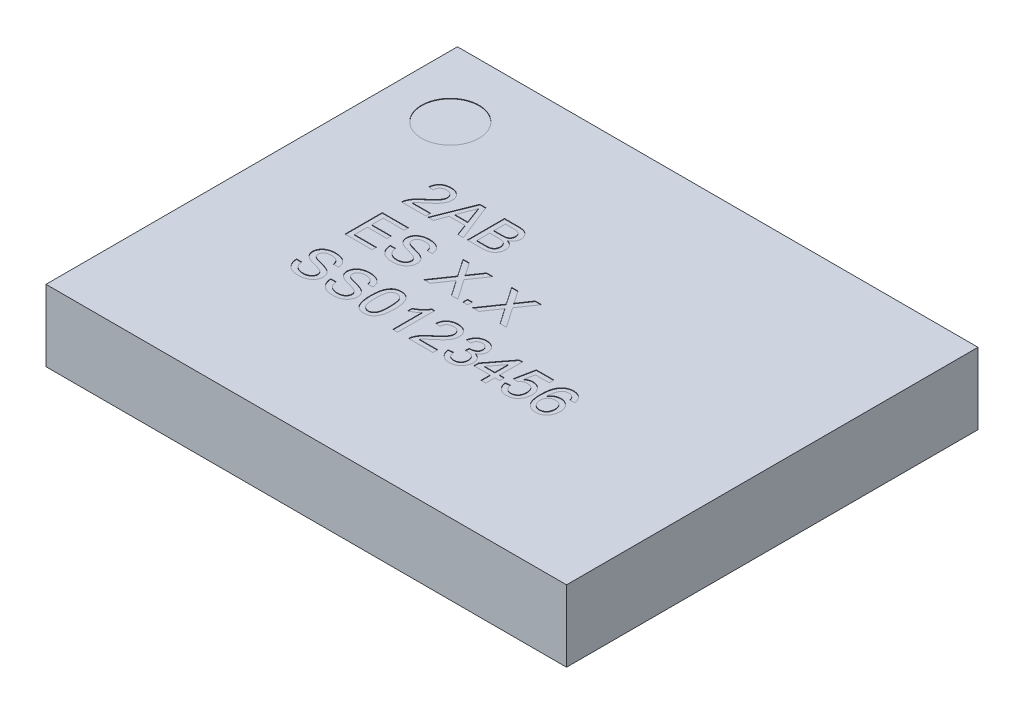
SolidWorks part; units mm, degrees
ref_plane "Front Plane" through (0, 0, 0) normal (0, 0, 1) x (1, 0, 0)
ref_plane "Top Plane" through (0, 0, 0) normal (0, 1, 0) x (1, 0, 0)
ref_plane "Right Plane" through (0, 0, 0) normal (1, 0, 0) x (0, 0, -1)
sketch "Sketch1" plane through (0, 0, 0) normal (0, 1, 0) x (1, 0, 0)
  line L1 (-5.25, -4.15) -> (5.25, -4.15)
  line L2 (-5.25, -4.15) -> (-5.25, 4.15)
  line L3 (-5.25, 4.15) -> (5.25, 4.15)
  line L4 (5.25, -4.15) -> (5.25, 4.15)
  line L5 (-5.25, -4.15) -> (5.25, 4.15) construction
  line L6 (-5.25, 4.15) -> (5.25, -4.15) construction
  point P0 (0, 0)
  dimension "D1" = 10.5
  dimension "D2" = 8.3
extrude "Boss-Extrude1" add sketch "Sketch1" along normal blind 1.44
sketch "Sketch3" plane through (0, 0, 0) normal (0, -1, 0) x (1, 0, 0)
  line L0 (-5.25, 4.15) -> (5.25, 4.15) construction
  line L1 (-4.95, 2.85) -> (-4.5, 2.85)
  line L2 (-4.95, 2.85) -> (-4.95, 3.15)
  line L3 (-4.95, 3.15) -> (-4.5, 3.15)
  line L4 (-4.5, 2.85) -> (-4.5, 3.15)
  line L5 (-4.95, 2.85) -> (-4.5, 3.15) construction
  line L6 (-4.95, 3.15) -> (-4.5, 2.85) construction
  line L7 (-5.25, -4.15) -> (-5.25, 4.15) construction
  line L8 (-4.95, 2.25) -> (-4.95, 2.55)
  line L9 (-4.95, 2.25) -> (-4.5, 2.25)
  line L10 (-4.5, 2.25) -> (-4.5, 2.55)
  line L11 (-4.95, 2.55) -> (-4.5, 2.55)
  line L12 (-4.95, 1.65) -> (-4.95, 1.95)
  line L13 (-4.95, 1.65) -> (-4.5, 1.65)
  line L14 (-4.5, 1.65) -> (-4.5, 1.95)
  line L15 (-4.95, 1.95) -> (-4.5, 1.95)
  line L16 (-4.95, 1.05) -> (-4.95, 1.35)
  line L17 (-4.95, 1.05) -> (-4.5, 1.05)
  line L18 (-4.5, 1.05) -> (-4.5, 1.35)
  line L19 (-4.95, 1.35) -> (-4.5, 1.35)
  line L20 (-4.95, 0.45) -> (-4.95, 0.75)
  line L21 (-4.95, 0.45) -> (-4.5, 0.45)
  line L22 (-4.5, 0.45) -> (-4.5, 0.75)
  line L23 (-4.95, 0.75) -> (-4.5, 0.75)
  line L24 (-4.95, -0.15) -> (-4.95, 0.15)
  line L25 (-4.95, -0.15) -> (-4.5, -0.15)
  line L26 (-4.5, -0.15) -> (-4.5, 0.15)
  line L27 (-4.95, 0.15) -> (-4.5, 0.15)
  line L28 (-4.95, -0.75) -> (-4.95, -0.45)
  line L29 (-4.95, -0.75) -> (-4.5, -0.75)
  line L30 (-4.5, -0.75) -> (-4.5, -0.45)
  line L31 (-4.95, -0.45) -> (-4.5, -0.45)
  line L32 (-4.95, -1.35) -> (-4.95, -1.05)
  line L33 (-4.95, -1.35) -> (-4.5, -1.35)
  line L34 (-4.5, -1.35) -> (-4.5, -1.05)
  line L35 (-4.95, -1.05) -> (-4.5, -1.05)
  line L36 (-4.95, -1.95) -> (-4.95, -1.65)
  line L37 (-4.95, -1.95) -> (-4.5, -1.95)
  line L38 (-4.5, -1.95) -> (-4.5, -1.65)
  line L39 (-4.95, -1.65) -> (-4.5, -1.65)
  line L40 (-4.95, -2.55) -> (-4.95, -2.25)
  line L41 (-4.95, -2.55) -> (-4.5, -2.55)
  line L42 (-4.5, -2.55) -> (-4.5, -2.25)
  line L43 (-4.95, -2.25) -> (-4.5, -2.25)
  line L44 (-4.95, -3.15) -> (-4.95, -2.85)
  line L45 (-4.95, -3.15) -> (-4.5, -3.15)
  line L46 (-4.5, -3.15) -> (-4.5, -2.85)
  line L47 (-4.95, -2.85) -> (-4.5, -2.85)
  line L48 (-4.35, 3.4) -> (-5.25, 3.4) construction
  line L49 (4.5, 2.85) -> (4.95, 2.85)
  line L50 (4.5, 2.85) -> (4.5, 3.15)
  line L51 (4.5, 3.15) -> (4.95, 3.15)
  line L52 (4.95, 2.85) -> (4.95, 3.15)
  line L53 (4.5, 2.85) -> (4.95, 3.15) construction
  line L54 (4.5, 3.15) -> (4.95, 2.85) construction
  line L55 (-4.35, 3.4) -> (-4.05, 3.4)
  line L56 (4.95, 3.15) -> (5.25, 3.15) construction
  line L57 (5.25, 4.15) -> (5.25, -4.15) construction
  line L58 (-4.95, 3.15) -> (-5.25, 3.15) construction
  line L59 (4.95, 3.15) -> (4.95, 4.15) construction
  line L60 (-4.5, 3.15) -> (-4.5, 4.15) construction
  line L61 (-4.95, 2.55) -> (-4.95, 2.85) construction
  line L62 (4.5, 2.25) -> (4.95, 2.25)
  line L63 (4.95, 2.25) -> (4.95, 2.55)
  line L64 (4.5, 2.55) -> (4.95, 2.55)
  line L65 (4.5, 2.25) -> (4.5, 2.55)
  line L66 (4.5, 1.65) -> (4.95, 1.65)
  line L67 (4.95, 1.65) -> (4.95, 1.95)
  line L68 (4.5, 1.95) -> (4.95, 1.95)
  line L69 (4.5, 1.65) -> (4.5, 1.95)
  line L70 (4.5, 1.05) -> (4.95, 1.05)
  line L71 (4.95, 1.05) -> (4.95, 1.35)
  line L72 (4.5, 1.35) -> (4.95, 1.35)
  line L73 (4.5, 1.05) -> (4.5, 1.35)
  line L74 (4.5, 0.45) -> (4.95, 0.45)
  line L75 (4.95, 0.45) -> (4.95, 0.75)
  line L76 (4.5, 0.75) -> (4.95, 0.75)
  line L77 (4.5, 0.45) -> (4.5, 0.75)
  line L78 (4.5, -0.15) -> (4.95, -0.15)
  line L79 (4.95, -0.15) -> (4.95, 0.15)
  line L80 (4.5, 0.15) -> (4.95, 0.15)
  line L81 (4.5, -0.15) -> (4.5, 0.15)
  line L82 (4.5, -0.75) -> (4.95, -0.75)
  line L83 (4.95, -0.75) -> (4.95, -0.45)
  line L84 (4.5, -0.45) -> (4.95, -0.45)
  line L85 (4.5, -0.75) -> (4.5, -0.45)
  line L86 (4.5, -1.35) -> (4.95, -1.35)
  line L87 (4.95, -1.35) -> (4.95, -1.05)
  line L88 (4.5, -1.05) -> (4.95, -1.05)
  line L89 (4.5, -1.35) -> (4.5, -1.05)
  line L90 (4.5, -1.95) -> (4.95, -1.95)
  line L91 (4.95, -1.95) -> (4.95, -1.65)
  line L92 (4.5, -1.65) -> (4.95, -1.65)
  line L93 (4.5, -1.95) -> (4.5, -1.65)
  line L94 (4.5, -2.55) -> (4.95, -2.55)
  line L95 (4.95, -2.55) -> (4.95, -2.25)
  line L96 (4.5, -2.25) -> (4.95, -2.25)
  line L97 (4.5, -2.55) -> (4.5, -2.25)
  line L98 (4.5, -3.15) -> (4.95, -3.15)
  line L99 (4.95, -3.15) -> (4.95, -2.85)
  line L100 (4.5, -2.85) -> (4.95, -2.85)
  line L101 (4.5, -3.15) -> (4.5, -2.85)
  line L102 (4.5, 2.55) -> (4.5, 2.85) construction
  line L103 (-4.35, -3.85) -> (-5.25, -3.85) construction
  line L104 (-4.35, -3.85) -> (-4.05, -3.85)
  line L105 (-4.35, -3.85) -> (-4.35, -3.4)
  line L106 (-4.35, -3.4) -> (-4.05, -3.4)
  line L107 (-4.05, -3.85) -> (-4.05, -3.4)
  line L108 (-4.35, -3.85) -> (-4.05, -3.4) construction
  line L109 (-4.35, -3.4) -> (-4.05, -3.85) construction
  line L110 (-4.35, -3.85) -> (-4.35, -4.15) construction
  line L111 (5.25, -4.15) -> (-5.25, -4.15) construction
  line L112 (-4.35, 3.4) -> (-4.35, 3.85)
  line L113 (-4.35, 3.85) -> (-4.05, 3.85)
  line L114 (-4.05, 3.4) -> (-4.05, 3.85)
  line L115 (-4.35, 3.4) -> (-4.05, 3.85) construction
  line L116 (-4.35, 3.85) -> (-4.05, 3.4) construction
  line L117 (-4.05, 3.85) -> (-4.05, 4.15) construction
  line L118 (-3.75, 3.4) -> (-3.45, 3.4)
  line L119 (-3.45, 3.4) -> (-3.45, 3.85)
  line L120 (-3.75, 3.85) -> (-3.45, 3.85)
  line L121 (-3.75, 3.4) -> (-3.75, 3.85)
  line L122 (-3.75, -3.85) -> (-3.75, -3.4)
  line L123 (-3.75, -3.85) -> (-3.45, -3.85)
  line L124 (-3.45, -3.85) -> (-3.45, -3.4)
  line L125 (-3.75, -3.4) -> (-3.45, -3.4)
  line L126 (-3.15, 3.4) -> (-2.85, 3.4)
  line L127 (-2.85, 3.4) -> (-2.85, 3.85)
  line L128 (-3.15, 3.85) -> (-2.85, 3.85)
  line L129 (-3.15, 3.4) -> (-3.15, 3.85)
  line L130 (-3.15, -3.85) -> (-3.15, -3.4)
  line L131 (-3.15, -3.85) -> (-2.85, -3.85)
  line L132 (-2.85, -3.85) -> (-2.85, -3.4)
  line L133 (-3.15, -3.4) -> (-2.85, -3.4)
  line L134 (-2.55, 3.4) -> (-2.25, 3.4)
  line L135 (-2.25, 3.4) -> (-2.25, 3.85)
  line L136 (-2.55, 3.85) -> (-2.25, 3.85)
  line L137 (-2.55, 3.4) -> (-2.55, 3.85)
  line L138 (-2.55, -3.85) -> (-2.55, -3.4)
  line L139 (-2.55, -3.85) -> (-2.25, -3.85)
  line L140 (-2.25, -3.85) -> (-2.25, -3.4)
  line L141 (-2.55, -3.4) -> (-2.25, -3.4)
  line L142 (-1.95, 3.4) -> (-1.65, 3.4)
  line L143 (-1.65, 3.4) -> (-1.65, 3.85)
  line L144 (-1.95, 3.85) -> (-1.65, 3.85)
  line L145 (-1.95, 3.4) -> (-1.95, 3.85)
  line L146 (-1.95, -3.85) -> (-1.95, -3.4)
  line L147 (-1.95, -3.85) -> (-1.65, -3.85)
  line L148 (-1.65, -3.85) -> (-1.65, -3.4)
  line L149 (-1.95, -3.4) -> (-1.65, -3.4)
  line L150 (-1.35, 3.4) -> (-1.05, 3.4)
  line L151 (-1.05, 3.4) -> (-1.05, 3.85)
  line L152 (-1.35, 3.85) -> (-1.05, 3.85)
  line L153 (-1.35, 3.4) -> (-1.35, 3.85)
  line L154 (-1.35, -3.85) -> (-1.35, -3.4)
  line L155 (-1.35, -3.85) -> (-1.05, -3.85)
  line L156 (-1.05, -3.85) -> (-1.05, -3.4)
  line L157 (-1.35, -3.4) -> (-1.05, -3.4)
  line L158 (-0.75, 3.4) -> (-0.45, 3.4)
  line L159 (-0.45, 3.4) -> (-0.45, 3.85)
  line L160 (-0.75, 3.85) -> (-0.45, 3.85)
  line L161 (-0.75, 3.4) -> (-0.75, 3.85)
  line L162 (-0.75, -3.85) -> (-0.75, -3.4)
  line L163 (-0.75, -3.85) -> (-0.45, -3.85)
  line L164 (-0.45, -3.85) -> (-0.45, -3.4)
  line L165 (-0.75, -3.4) -> (-0.45, -3.4)
  line L166 (-0.15, 3.4) -> (0.15, 3.4)
  line L167 (0.15, 3.4) -> (0.15, 3.85)
  line L168 (-0.15, 3.85) -> (0.15, 3.85)
  line L169 (-0.15, 3.4) -> (-0.15, 3.85)
  line L170 (-0.15, -3.85) -> (-0.15, -3.4)
  line L171 (-0.15, -3.85) -> (0.15, -3.85)
  line L172 (0.15, -3.85) -> (0.15, -3.4)
  line L173 (-0.15, -3.4) -> (0.15, -3.4)
  line L174 (0.45, 3.4) -> (0.75, 3.4)
  line L175 (0.75, 3.4) -> (0.75, 3.85)
  line L176 (0.45, 3.85) -> (0.75, 3.85)
  line L177 (0.45, 3.4) -> (0.45, 3.85)
  line L178 (0.45, -3.85) -> (0.45, -3.4)
  line L179 (0.45, -3.85) -> (0.75, -3.85)
  line L180 (0.75, -3.85) -> (0.75, -3.4)
  line L181 (0.45, -3.4) -> (0.75, -3.4)
  line L182 (1.05, 3.4) -> (1.35, 3.4)
  line L183 (1.35, 3.4) -> (1.35, 3.85)
  line L184 (1.05, 3.85) -> (1.35, 3.85)
  line L185 (1.05, 3.4) -> (1.05, 3.85)
  line L186 (1.05, -3.85) -> (1.05, -3.4)
  line L187 (1.05, -3.85) -> (1.35, -3.85)
  line L188 (1.35, -3.85) -> (1.35, -3.4)
  line L189 (1.05, -3.4) -> (1.35, -3.4)
  line L190 (1.65, 3.4) -> (1.95, 3.4)
  line L191 (1.95, 3.4) -> (1.95, 3.85)
  line L192 (1.65, 3.85) -> (1.95, 3.85)
  line L193 (1.65, 3.4) -> (1.65, 3.85)
  line L194 (1.65, -3.85) -> (1.65, -3.4)
  line L195 (1.65, -3.85) -> (1.95, -3.85)
  line L196 (1.95, -3.85) -> (1.95, -3.4)
  line L197 (1.65, -3.4) -> (1.95, -3.4)
  line L198 (2.25, 3.4) -> (2.55, 3.4)
  line L199 (2.55, 3.4) -> (2.55, 3.85)
  line L200 (2.25, 3.85) -> (2.55, 3.85)
  line L201 (2.25, 3.4) -> (2.25, 3.85)
  line L202 (2.25, -3.85) -> (2.25, -3.4)
  line L203 (2.25, -3.85) -> (2.55, -3.85)
  line L204 (2.55, -3.85) -> (2.55, -3.4)
  line L205 (2.25, -3.4) -> (2.55, -3.4)
  line L206 (2.85, 3.4) -> (3.15, 3.4)
  line L207 (3.15, 3.4) -> (3.15, 3.85)
  line L208 (2.85, 3.85) -> (3.15, 3.85)
  line L209 (2.85, 3.4) -> (2.85, 3.85)
  line L210 (2.85, -3.85) -> (2.85, -3.4)
  line L211 (2.85, -3.85) -> (3.15, -3.85)
  line L212 (3.15, -3.85) -> (3.15, -3.4)
  line L213 (2.85, -3.4) -> (3.15, -3.4)
  line L214 (3.45, 3.4) -> (3.75, 3.4)
  line L215 (3.75, 3.4) -> (3.75, 3.85)
  line L216 (3.45, 3.85) -> (3.75, 3.85)
  line L217 (3.45, 3.4) -> (3.45, 3.85)
  line L218 (3.45, -3.85) -> (3.45, -3.4)
  line L219 (3.45, -3.85) -> (3.75, -3.85)
  line L220 (3.75, -3.85) -> (3.75, -3.4)
  line L221 (3.45, -3.4) -> (3.75, -3.4)
  line L222 (4.05, 3.4) -> (4.35, 3.4)
  line L223 (4.35, 3.4) -> (4.35, 3.85)
  line L224 (4.05, 3.85) -> (4.35, 3.85)
  line L225 (4.05, 3.4) -> (4.05, 3.85)
  line L226 (4.05, -3.85) -> (4.05, -3.4)
  line L227 (4.05, -3.85) -> (4.35, -3.85)
  line L228 (4.35, -3.85) -> (4.35, -3.4)
  line L229 (4.05, -3.4) -> (4.35, -3.4)
  line L230 (-3.75, -2.85) -> (-3.3, -2.85)
  line L231 (-3.75, -2.85) -> (-3.75, -2.55)
  line L232 (-3.75, -2.55) -> (-3.3, -2.55)
  line L233 (-3.3, -2.85) -> (-3.3, -2.55)
  line L234 (-3.75, -2.85) -> (-3.3, -2.55) construction
  line L235 (-3.75, -2.55) -> (-3.3, -2.85) construction
  line L236 (-4.5, -2.55) -> (-4.5, -2.85) construction
  line L237 (3.3, -2.85) -> (3.75, -2.85)
  line L238 (3.3, -2.85) -> (3.3, -2.55)
  line L239 (3.3, -2.55) -> (3.75, -2.55)
  line L240 (3.75, -2.85) -> (3.75, -2.55)
  line L241 (3.3, -2.85) -> (3.75, -2.55) construction
  line L242 (3.3, -2.55) -> (3.75, -2.85) construction
  line L243 (3.75, -2.85) -> (5.25, -2.85) construction
  line L244 (-3.75, -2.85) -> (-5.25, -2.85) construction
  line L245 (-3.75, -2.25) -> (-3.3, -2.25)
  line L246 (-3.3, -2.25) -> (-3.3, -1.95)
  line L247 (-3.75, -1.95) -> (-3.3, -1.95)
  line L248 (-3.75, -2.25) -> (-3.75, -1.95)
  line L249 (3.3, -2.25) -> (3.75, -2.25)
  line L250 (3.75, -2.25) -> (3.75, -1.95)
  line L251 (3.3, -1.95) -> (3.75, -1.95)
  line L252 (3.3, -2.25) -> (3.3, -1.95)
  line L253 (-3.75, -1.65) -> (-3.3, -1.65)
  line L254 (-3.3, -1.65) -> (-3.3, -1.35)
  line L255 (-3.75, -1.35) -> (-3.3, -1.35)
  line L256 (-3.75, -1.65) -> (-3.75, -1.35)
  line L257 (3.3, -1.65) -> (3.75, -1.65)
  line L258 (3.75, -1.65) -> (3.75, -1.35)
  line L259 (3.3, -1.35) -> (3.75, -1.35)
  line L260 (3.3, -1.65) -> (3.3, -1.35)
  line L261 (-3.75, -1.05) -> (-3.3, -1.05)
  line L262 (-3.3, -1.05) -> (-3.3, -0.75)
  line L263 (-3.75, -0.75) -> (-3.3, -0.75)
  line L264 (-3.75, -1.05) -> (-3.75, -0.75)
  line L265 (3.3, -1.05) -> (3.75, -1.05)
  line L266 (3.75, -1.05) -> (3.75, -0.75)
  line L267 (3.3, -0.75) -> (3.75, -0.75)
  line L268 (3.3, -1.05) -> (3.3, -0.75)
  line L269 (-3.75, -0.45) -> (-3.3, -0.45)
  line L270 (-3.3, -0.45) -> (-3.3, -0.15)
  line L271 (-3.75, -0.15) -> (-3.3, -0.15)
  line L272 (-3.75, -0.45) -> (-3.75, -0.15)
  line L273 (3.3, -0.45) -> (3.75, -0.45)
  line L274 (3.75, -0.45) -> (3.75, -0.15)
  line L275 (3.3, -0.15) -> (3.75, -0.15)
  line L276 (3.3, -0.45) -> (3.3, -0.15)
  line L277 (-3.75, 0.15) -> (-3.3, 0.15)
  line L278 (-3.3, 0.15) -> (-3.3, 0.45)
  line L279 (-3.75, 0.45) -> (-3.3, 0.45)
  line L280 (-3.75, 0.15) -> (-3.75, 0.45)
  line L281 (3.3, 0.15) -> (3.75, 0.15)
  line L282 (3.75, 0.15) -> (3.75, 0.45)
  line L283 (3.3, 0.45) -> (3.75, 0.45)
  line L284 (3.3, 0.15) -> (3.3, 0.45)
  line L285 (-3.75, 0.75) -> (-3.3, 0.75)
  line L286 (-3.3, 0.75) -> (-3.3, 1.05)
  line L287 (-3.75, 1.05) -> (-3.3, 1.05)
  line L288 (-3.75, 0.75) -> (-3.75, 1.05)
  line L289 (3.3, 0.75) -> (3.75, 0.75)
  line L290 (3.75, 0.75) -> (3.75, 1.05)
  line L291 (3.3, 1.05) -> (3.75, 1.05)
  line L292 (3.3, 0.75) -> (3.3, 1.05)
  line L293 (-3.75, 1.35) -> (-3.3, 1.35)
  line L294 (-3.3, 1.35) -> (-3.3, 1.65)
  line L295 (-3.75, 1.65) -> (-3.3, 1.65)
  line L296 (-3.75, 1.35) -> (-3.75, 1.65)
  line L297 (3.3, 1.35) -> (3.75, 1.35)
  line L298 (3.75, 1.35) -> (3.75, 1.65)
  line L299 (3.3, 1.65) -> (3.75, 1.65)
  line L300 (3.3, 1.35) -> (3.3, 1.65)
  line L301 (-3.75, 1.95) -> (-3.3, 1.95)
  line L302 (-3.3, 1.95) -> (-3.3, 2.25)
  line L303 (-3.75, 2.25) -> (-3.3, 2.25)
  line L304 (-3.75, 1.95) -> (-3.75, 2.25)
  line L305 (3.3, 1.95) -> (3.75, 1.95)
  line L306 (3.75, 1.95) -> (3.75, 2.25)
  line L307 (3.3, 2.25) -> (3.75, 2.25)
  line L308 (3.3, 1.95) -> (3.3, 2.25)
  line L309 (-3.75, 2.55) -> (-3.3, 2.55)
  line L310 (-3.3, 2.55) -> (-3.3, 2.85)
  line L311 (-3.75, 2.85) -> (-3.3, 2.85)
  line L312 (-3.75, 2.55) -> (-3.75, 2.85)
  line L313 (3.3, 2.55) -> (3.75, 2.55)
  line L314 (3.75, 2.55) -> (3.75, 2.85)
  line L315 (3.3, 2.85) -> (3.75, 2.85)
  line L316 (3.3, 2.55) -> (3.3, 2.85)
  line L317 (-2.225, -2.55) -> (-1.775, -2.55)
  line L318 (-2.225, -2.55) -> (-2.225, -2.25)
  line L319 (-2.225, -2.25) -> (-1.775, -2.25)
  line L320 (-1.775, -2.55) -> (-1.775, -2.25)
  line L321 (-2.225, -2.55) -> (-1.775, -2.25) construction
  line L322 (-2.225, -2.25) -> (-1.775, -2.55) construction
  line L323 (-1.225, -2.55) -> (-0.775, -2.55)
  line L324 (-0.775, -2.55) -> (-0.775, -2.25)
  line L325 (-1.225, -2.25) -> (-0.775, -2.25)
  line L326 (-1.225, -2.55) -> (-1.225, -2.25)
  line L327 (-0.225, -2.55) -> (0.225, -2.55)
  line L328 (0.225, -2.55) -> (0.225, -2.25)
  line L329 (-0.225, -2.25) -> (0.225, -2.25)
  line L330 (-0.225, -2.55) -> (-0.225, -2.25)
  line L331 (0.775, -2.55) -> (1.225, -2.55)
  line L332 (1.225, -2.55) -> (1.225, -2.25)
  line L333 (0.775, -2.25) -> (1.225, -2.25)
  line L334 (0.775, -2.55) -> (0.775, -2.25)
  line L335 (1.775, -2.55) -> (2.225, -2.55)
  line L336 (2.225, -2.55) -> (2.225, -2.25)
  line L337 (1.775, -2.25) -> (2.225, -2.25)
  line L338 (1.775, -2.55) -> (1.775, -2.25)
  line L339 (-1.225, -1.35) -> (-0.775, -1.35)
  line L340 (-0.775, -1.35) -> (-0.775, -1.05)
  line L341 (-1.225, -1.05) -> (-0.775, -1.05)
  line L342 (-1.225, -1.35) -> (-1.225, -1.05)
  line L343 (-0.225, -1.35) -> (0.225, -1.35)
  line L344 (0.225, -1.35) -> (0.225, -1.05)
  line L345 (-0.225, -1.05) -> (0.225, -1.05)
  line L346 (-0.225, -1.35) -> (-0.225, -1.05)
  line L347 (0.775, -1.35) -> (1.225, -1.35)
  line L348 (1.225, -1.35) -> (1.225, -1.05)
  line L349 (0.775, -1.05) -> (1.225, -1.05)
  line L350 (0.775, -1.35) -> (0.775, -1.05)
  line L351 (1.775, -1.35) -> (2.225, -1.35)
  line L352 (2.225, -1.35) -> (2.225, -1.05)
  line L353 (1.775, -1.05) -> (2.225, -1.05)
  line L354 (1.775, -1.35) -> (1.775, -1.05)
  line L355 (-1.225, -0.15) -> (-0.775, -0.15)
  line L356 (-0.775, -0.15) -> (-0.775, 0.15)
  line L357 (-1.225, 0.15) -> (-0.775, 0.15)
  line L358 (-1.225, -0.15) -> (-1.225, 0.15)
  line L359 (-0.225, -0.15) -> (0.225, -0.15)
  line L360 (0.225, -0.15) -> (0.225, 0.15)
  line L361 (-0.225, 0.15) -> (0.225, 0.15)
  line L362 (-0.225, -0.15) -> (-0.225, 0.15)
  line L363 (0.775, -0.15) -> (1.225, -0.15)
  line L364 (1.225, -0.15) -> (1.225, 0.15)
  line L365 (0.775, 0.15) -> (1.225, 0.15)
  line L366 (0.775, -0.15) -> (0.775, 0.15)
  line L367 (1.775, -0.15) -> (2.225, -0.15)
  line L368 (2.225, -0.15) -> (2.225, 0.15)
  line L369 (1.775, 0.15) -> (2.225, 0.15)
  line L370 (1.775, -0.15) -> (1.775, 0.15)
  line L371 (-1.225, 1.05) -> (-0.775, 1.05)
  line L372 (-0.775, 1.05) -> (-0.775, 1.35)
  line L373 (-1.225, 1.35) -> (-0.775, 1.35)
  line L374 (-1.225, 1.05) -> (-1.225, 1.35)
  line L375 (-0.225, 1.05) -> (0.225, 1.05)
  line L376 (0.225, 1.05) -> (0.225, 1.35)
  line L377 (-0.225, 1.35) -> (0.225, 1.35)
  line L378 (-0.225, 1.05) -> (-0.225, 1.35)
  line L379 (0.775, 1.05) -> (1.225, 1.05)
  line L380 (1.225, 1.05) -> (1.225, 1.35)
  line L381 (0.775, 1.35) -> (1.225, 1.35)
  line L382 (0.775, 1.05) -> (0.775, 1.35)
  line L383 (1.775, 1.05) -> (2.225, 1.05)
  line L384 (2.225, 1.05) -> (2.225, 1.35)
  line L385 (1.775, 1.35) -> (2.225, 1.35)
  line L386 (1.775, 1.05) -> (1.775, 1.35)
  line L387 (-1.225, 2.25) -> (-0.775, 2.25)
  line L388 (-0.775, 2.25) -> (-0.775, 2.55)
  line L389 (-1.225, 2.55) -> (-0.775, 2.55)
  line L390 (-1.225, 2.25) -> (-1.225, 2.55)
  line L391 (-0.225, 2.25) -> (0.225, 2.25)
  line L392 (0.225, 2.25) -> (0.225, 2.55)
  line L393 (-0.225, 2.55) -> (0.225, 2.55)
  line L394 (-0.225, 2.25) -> (-0.225, 2.55)
  line L395 (0.775, 2.25) -> (1.225, 2.25)
  line L396 (1.225, 2.25) -> (1.225, 2.55)
  line L397 (0.775, 2.55) -> (1.225, 2.55)
  line L398 (0.775, 2.25) -> (0.775, 2.55)
  line L399 (1.775, 2.25) -> (2.225, 2.25)
  line L400 (2.225, 2.25) -> (2.225, 2.55)
  line L401 (1.775, 2.55) -> (2.225, 2.55)
  line L402 (1.775, 2.25) -> (1.775, 2.55)
  line L403 (-2.225, -1.35) -> (-1.775, -1.35)
  line L404 (-1.775, -1.35) -> (-1.775, -1.05)
  line L405 (-2.225, -1.05) -> (-1.775, -1.05)
  line L406 (-2.225, -1.35) -> (-2.225, -1.05)
  line L407 (-2.225, -0.15) -> (-1.775, -0.15)
  line L408 (-1.775, -0.15) -> (-1.775, 0.15)
  line L409 (-2.225, 0.15) -> (-1.775, 0.15)
  line L410 (-2.225, -0.15) -> (-2.225, 0.15)
  line L411 (-2.225, 1.05) -> (-1.775, 1.05)
  line L412 (-1.775, 1.05) -> (-1.775, 1.35)
  line L413 (-2.225, 1.35) -> (-1.775, 1.35)
  line L414 (-2.225, 1.05) -> (-2.225, 1.35)
  line L415 (-2.225, 2.25) -> (-1.775, 2.25)
  line L416 (-1.775, 2.25) -> (-1.775, 2.55)
  line L417 (-2.225, 2.55) -> (-1.775, 2.55)
  line L418 (-2.225, 2.25) -> (-2.225, 2.55)
  point P0 (-4.725, 3)
  point P5 (4.725, 3)
  point P54 (-4.2, -3.625)
  point P105 (-4.2, 3.625)
  point P115 (-4.5, -2.7)
  point P117 (-3.525, -2.7)
  point P234 (3.525, -2.7)
  point P239 (-2, -2.4)
  dimension "D1" = 0.45
  dimension "D2" = 0.3
  dimension "D3" = 1
  dimension "D4" = 0.3
  dimension "D6" = 0.3
  dimension "D7" = 11
  dimension "D8" = 0.3
  dimension "D9" = 0.45
  dimension "D10" = 0.9
  dimension "D11" = 0.3
  dimension "D12" = 0.3
  dimension "D13" = 0.45
  dimension "D14" = 15
  dimension "D15" = 0.3
  dimension "D16" = 0.45
  dimension "D17" = 0.3
  dimension "D18" = 1.5
  dimension "D19" = 0.45
  dimension "D20" = 0.3
  dimension "D21" = 10
  dimension "D22" = 0.3
  dimension "D23" = 0.45
  dimension "D24" = 0.3
  dimension "D25" = 3.025
  dimension "D26" = 1.6
  dimension "D29" = 0.55
  dimension "D30" = 0.9
  dimension "D5" = 11
  dimension "D27" = 5
  dimension "D28" = 5
extrude "Boss-Extrude2" add sketch "Sketch3" along normal blind 0.045
sketch "Sketch4" plane through (0, 1.44, 0) normal (0, 1, 0) x (1, 0, 0)
  circle A0 centre (-4.0121, 2.7677) radius 0.5791
  text T0 "2AB" font "Arial" height 0.75
sketch "Sketch6" plane through (0, 1.44, 0) normal (0, 1, 0) x (1, 0, 0)
  text T0 "ES X.X\r\n" font "Arial" height 0.75
sketch "Sketch8" plane through (0, 1.44, 0) normal (0, 1, 0) x (1, 0, 0)
  text T0 "SS0123456" font "Arial" height 0.75
extrude "Cut-Extrude1" cut sketch "Sketch4" against normal blind 0.01
extrude "Cut-Extrude2" cut sketch "Sketch6" against normal blind 0.01
extrude "Cut-Extrude3" cut sketch "Sketch8" against normal blind 0.01
